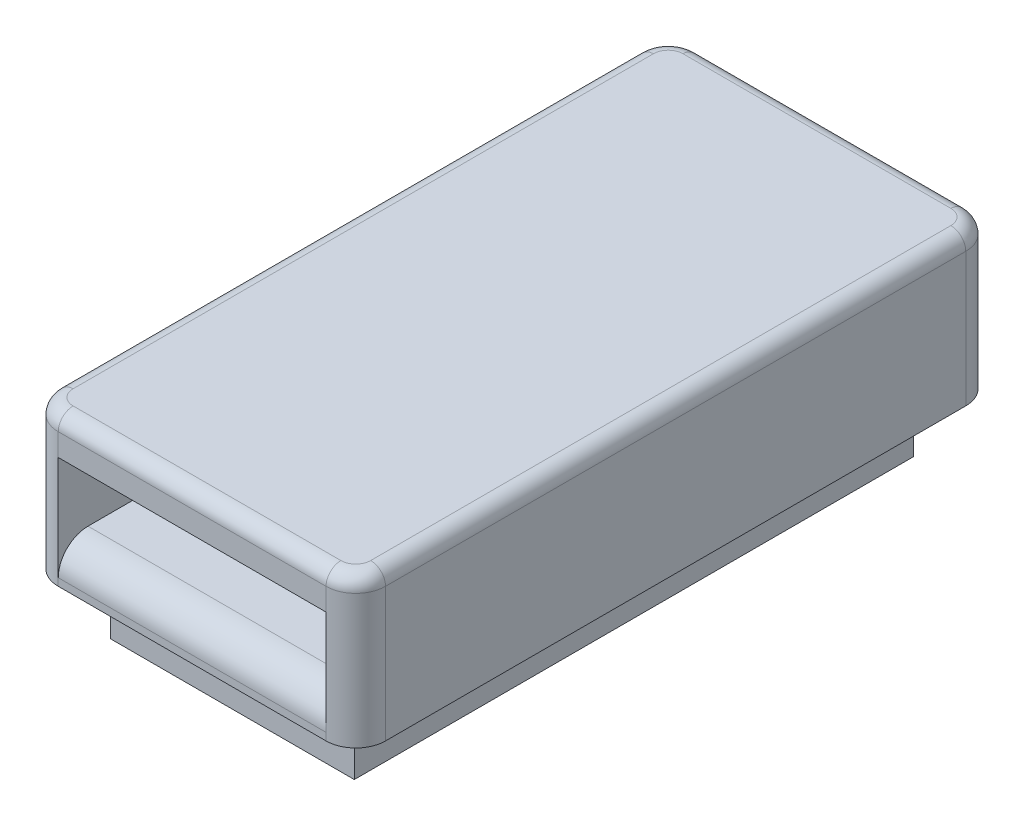
SolidWorks part; units mm, degrees
ref_plane "Front Plane" through (0, 0, 0) normal (0, 0, 1) x (1, 0, 0)
ref_plane "Top Plane" through (0, 0, 0) normal (0, 1, 0) x (1, 0, 0)
ref_plane "Right Plane" through (0, 0, 0) normal (1, 0, 0) x (0, 0, -1)
sketch "Sketch1" plane through (0, 0, 0) normal (0, 1, 0) x (1, 0, 0)
  line L1 (8.2, -18.8) -> (-8.2, -18.8)
  line L2 (8.2, -18.8) -> (8.2, 18.8)
  line L3 (8.2, 18.8) -> (-8.2, 18.8)
  line L4 (-8.2, -18.8) -> (-8.2, 18.8)
  line L5 (8.2, -18.8) -> (-8.2, 18.8) construction
  line L6 (8.2, 18.8) -> (-8.2, -18.8) construction
  line L7 (-9, -21.5) -> (9, -21.5)
  line L8 (-11, -19.5) -> (-11, 19.5)
  line L9 (-9, 21.5) -> (9, 21.5)
  line L10 (11, -19.5) -> (11, 19.5)
  line L11 (-11, -21.5) -> (11, 21.5) construction
  line L12 (-11, 21.5) -> (11, -21.5) construction
  arc A0 (-9, -21.5) -> (-11, -19.5) centre (-9, -19.5) cw
  arc A1 (9, -21.5) -> (11, -19.5) centre (9, -19.5) ccw
  arc A2 (9, 21.5) -> (11, 19.5) centre (9, 19.5) cw
  arc A3 (-11, 19.5) -> (-9, 21.5) centre (-9, 19.5) cw
  point P0 (0, 0)
  point P6 (0, 0)
  dimension "D5" = 2
  dimension "D1" = 16.4
  dimension "D2" = 37.6
  dimension "D3" = 22
  dimension "D4" = 43
extrude "Boss-Extrude1" add sketch "Sketch1" along normal blind 10 contours L9 A2 L10 A1 L7 A0 L8 A3
extrude "Boss-Extrude2" add sketch "Sketch1<4>" against normal blind 4 contours L4 L1 L2 L3 region at (0, 0, 0)
sketch "Sketch1<4>" plane through (0, 0, 0) normal (0, 1, 0) x (1, 0, 0) same geometry as "Sketch1"
sketch "Sketch3" plane through (-43, 0, -21.5) normal (0, 0, 1) x (1, 0, 0)
  line L0 (34, 10) -> (52, 10) construction
  line L1 (34, 7.5) -> (52, 7.5)
  line L2 (34, 7.5) -> (34, 2.5)
  line L3 (34, 2.5) -> (52, 2.5)
  line L4 (52, 7.5) -> (52, 2.5)
  point P6 (43, 2.5)
  dimension "D1" = 18
  dimension "D2" = 5
  dimension "D3" = 2.5
extrude "Cut-Extrude2" cut sketch "Sketch3" along normal through all contours L4 L3 L2 L1
fillet "Fillet2" radius 1 8 edges at (-10.4142, 10, 20.9142) (-11, 10, 0) (-10.4142, 10, -20.9142) (0, 10, -21.5) (10.4142, 10, -20.9142) (11, 10, 0) (10.4142, 10, 20.9142) (0, 10, 21.5)
fillet "Fillet3" radius 2 2 edges at (0, 2.5, 21.5) (0, 2.5, -21.5)
